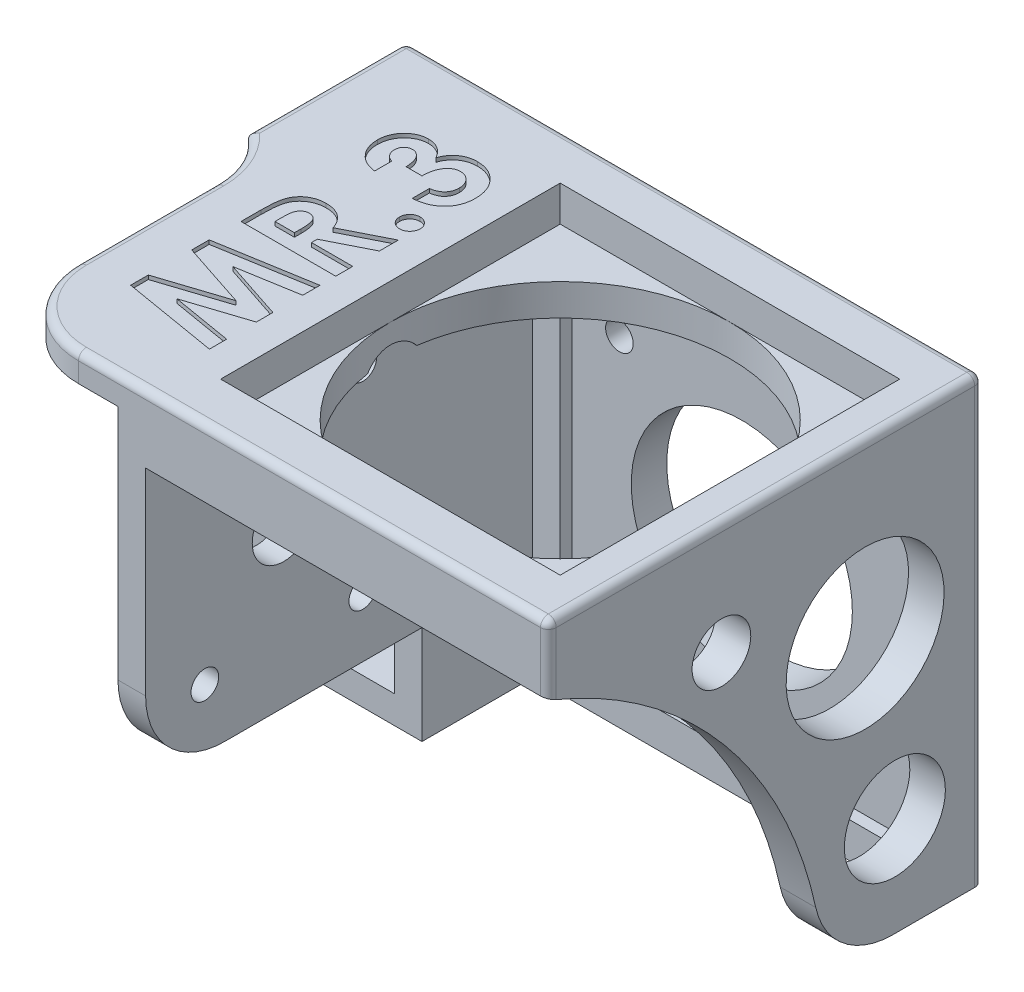
SolidWorks part; units mm, degrees
ref_plane "Front Plane" through (0, 0, 0) normal (0, 0, 1) x (1, 0, 0)
ref_plane "Top Plane" through (0, 0, 0) normal (0, 1, 0) x (1, 0, 0)
ref_plane "Right Plane" through (0, 0, 0) normal (1, 0, 0) x (0, 0, -1)
sketch "Sketch1" plane through (0, 0, 0) normal (0, 0, 1) x (1, 0, 0)
  line L0 (-36.7771, -12.6028) -> (36.2229, -12.6028)
  line L1 (-36.7771, 43.3972) -> (-14.7771, 43.3972)
  line L2 (-36.7771, 43.3972) -> (-36.7771, -12.6028)
  line L3 (36.2229, -12.6028) -> (36.2229, 43.3972)
  line L5 (-33.2771, 39.8972) -> (-18.2771, 39.8972)
  line L6 (-33.2771, 39.8972) -> (-33.2771, 24.8972)
  line L7 (-33.2771, 24.8972) -> (-18.2771, 24.8972)
  line L8 (-18.2771, 39.8972) -> (-18.2771, 24.8972)
  line L9 (-14.7771, 43.3972) -> (36.2229, 43.3972)
  dimension "D1" = 22
  dimension "D3" = 15
  dimension "D4" = 15
  dimension "D5" = 3.5
  dimension "D6" = 51
  dimension "D11" = 3.5
extrude "Boss-Extrude2" add sketch "Sketch1" along normal blind 20 contours L3 L9 L1 L2 L5 L8 L7 L6 region at (1.2081, 14.407, 0)
sketch "Sketch2" plane through (0, 0, 20) normal (0, 0, 1) x (1, 0, 0)
  line L0 (36.2229, -12.6028) -> (36.2229, 43.3972) construction
  line L1 (31.7229, -8.1028) -> (-11.2771, -8.1028)
  line L2 (31.7229, -8.1028) -> (31.7229, 34.8972)
  line L3 (31.7229, 34.8972) -> (-11.2771, 34.8972)
  line L4 (-11.2771, -8.1028) -> (-11.2771, 34.8972)
  line L5 (-36.7771, -12.6028) -> (36.2229, -12.6028) construction
  line L6 (-14.7771, 43.3972) -> (-14.7771, -12.6028) construction
  line L7 (-36.7771, 43.3972) -> (36.2229, 43.3972) construction
  line L8 (-18.2771, 39.8972) -> (-18.2771, 24.8972) construction
  line L9 (-33.2771, 24.8972) -> (-18.2771, 24.8972) construction
  line L10 (-33.2771, 14.8972) -> (-18.2771, 14.8972)
  line L11 (-33.2771, 14.8972) -> (-33.2771, -0.1028)
  line L12 (-33.2771, -0.1028) -> (-18.2771, -0.1028)
  line L13 (-18.2771, 14.8972) -> (-18.2771, -0.1028)
  line L14 (-36.7771, 43.3972) -> (-36.7771, -12.6028) construction
  dimension "D1" = 43
  dimension "D2" = 4.5
  dimension "D3" = 4.5
  dimension "D4" = 3.5
  dimension "D5" = 15
  dimension "D6" = 10
  dimension "D7" = 3.5
  dimension "D8" = 15
extrude "Cut-Extrude1" cut sketch "Sketch2" against normal offset from surface (15.5 mm away) 4.5 up to face at (-0.2771, 15.3972, 0)
sketch "Sketch3" plane through (0, 0, 4.5) normal (0, 0, 1) x (1, 0, 0)
  line L0 (-11.2771, -8.1028) -> (31.7229, 34.8972) construction
  line L1 (-11.2771, 34.8972) -> (31.7229, -8.1028) construction
  circle A0 centre (10.2229, 13.3972) radius 14
  circle A1 centre (25.7229, 28.8972) radius 1.75
  circle A2 centre (-5.2771, 28.8972) radius 1.75
  circle A3 centre (-5.2771, -2.1028) radius 1.75
  circle A4 centre (25.7229, -2.1028) radius 1.75
  dimension "D1" = 28
  dimension "D2" = 3.5
  dimension "D3" = 31
extrude "Cut-Extrude2" cut sketch "Sketch3" against normal blind 4.5
sketch "Sketch5" plane through (0, 0, 20) normal (0, 0, 1) x (1, 0, 0)
  line L0 (-33.2771, 39.8972) -> (-33.2771, 43.3972)
  line L1 (-33.2771, 43.3972) -> (-18.2771, 43.3972)
  line L2 (36.2229, -12.6028) -> (36.2229, 43.3972) construction
  line L3 (-33.2771, 39.8972) -> (-18.2771, 39.8972)
  line L4 (-14.7771, 43.3972) -> (36.2229, 43.3972)
  line L5 (-18.2771, 43.3972) -> (-14.7771, 43.3972)
  line L6 (-18.2771, 39.8972) -> (-18.2771, -0.1028)
  line L7 (-18.2771, -0.1028) -> (-14.7771, -0.1028)
  line L8 (-14.7771, 34.8972) -> (-14.7771, -0.1028)
  line L9 (31.7229, 34.8972) -> (-11.2771, 34.8972) construction
  line L10 (-14.7771, 34.8972) -> (36.2229, 34.8972)
  line L11 (36.2229, 43.3972) -> (36.2229, 34.8972)
  dimension "D1" = 3.5
extrude "Boss-Extrude3" add sketch "Sketch5" along normal blind 35
sketch "Sketch6" plane through (0, 43.3972, 0) normal (0, 1, 0) x (1, 0, 0)
  line L0 (36.2229, -55) -> (36.2229, 0) construction
  line L1 (31.7229, -6) -> (-11.2771, -6)
  line L2 (31.7229, -6) -> (31.7229, -49)
  line L3 (31.7229, -49) -> (-11.2771, -49)
  line L4 (-11.2771, -6) -> (-11.2771, -49)
  line L5 (-36.7771, 0) -> (36.2229, 0) construction
  dimension "D1" = 43
  dimension "D2" = 43
  dimension "D3" = 4.5
  dimension "D4" = 6
extrude "Cut-Extrude3" cut sketch "Sketch6" against normal offset from surface (4.5 mm away) 4 up to face at (9.9729, 34.8972, 25.125)
sketch "Sketch7" plane through (0, 38.8972, 0) normal (0, 1, 0) x (1, 0, 0)
  line L0 (-11.2771, -6) -> (31.7229, -49) construction
  line L1 (31.7229, -6) -> (-11.2771, -49) construction
  circle A0 centre (10.2229, -27.5) radius 21.5
extrude "Cut-Extrude4" cut sketch "Sketch7" against normal blind 4
sketch "Sketch8" plane through (-18.2771, 0, 0) normal (-1, 0, 0) x (0, 0, 1)
  line L0 (20, 24.8972) -> (55, 24.8972) construction
  line L1 (55, 39.8972) -> (55, -0.1028) construction
  line L2 (20, 14.8972) -> (55, 14.8972) construction
  line L3 (55, 32.3972) -> (20, 32.3972) construction
  line L4 (20, 43.3972) -> (20, -12.6028) construction
  line L5 (55, 7.3972) -> (23.2569, 7.3972) construction
  circle A0 centre (37.5, 19.8972) radius 4
  circle A1 centre (27.5, 32.3972) radius 1.75
  circle A2 centre (27.5, 7.3972) radius 1.75
  circle A3 centre (47.5, 7.3972) radius 1.75
  circle A4 centre (47.5, 32.3972) radius 1.75
  dimension "D2" = 8
  dimension "D7" = 17.5
  dimension "D8" = 3.5
  dimension "D1" = 5
  dimension "D3" = 20
  dimension "D4" = 20
  dimension "D5" = 7.5
  dimension "D6" = 7.5
  dimension "D9" = 7.5
  dimension "D10" = 7.5
extrude "Cut-Extrude5" cut sketch "Sketch8" against normal blind 4
sketch "Sketch9" plane through (0, 0, 20) normal (0, 0, 1) x (1, 0, 0)
  line L0 (-36.7771, -12.6028) -> (36.2229, -12.6028) construction
  line L1 (-11.2771, -8.1028) -> (31.7229, -8.1028)
  line L2 (-11.2771, -8.1028) -> (-11.2771, -12.6028)
  line L3 (-11.2771, -12.6028) -> (31.7229, -12.6028)
  line L4 (31.7229, -8.1028) -> (31.7229, -12.6028)
  line L5 (36.2229, -12.6028) -> (36.2229, 34.8972) construction
  dimension "D1" = 4.5
extrude "Cut-Extrude6" cut sketch "Sketch9" against normal offset from surface (14 mm away) 6 up to face at (27.4729, -2.1028, 0)
fillet "Fillet2" radius 10 1 edges at (-16.5271, -0.1028, 55)
sketch "Sketch10" plane through (-14.7771, 0, 0) normal (1, 0, 0) x (0, 0, -1)
  circle A0 centre (-27.5, 32.3972) radius 4
  circle A1 centre (-47.5, 32.3972) radius 4
  dimension "D1" = 8
  dimension "D2" = 8
extrude "Cut-Extrude7" cut sketch "Sketch10" along normal blind 9
sketch "Sketch11" plane through (36.2229, 0, 0) normal (1, 0, 0) x (0, 0, -1)
  line L1 (-20, -12.6028) -> (-20, 34.8972)
  line L2 (-20, 34.8972) -> (-55, 34.8972)
  arc A0 (-55, 34.8972) -> (-20, -12.6028) centre (-75.0615, -16.5297) cw
extrude "Boss-Extrude4" add sketch "Sketch11" against normal up to surface (4.5 mm away) up to face at (31.7229, 0.7722, 8.875)
fillet "Fillet3" radius 10 2 edges at (-33.2771, 41.6472, 55)
sketch "Sketch12" plane through (0, 0, 20) normal (0, 0, 1) x (1, 0, 0)
  line L1 (-14.7771, 34.8972) -> (-11.2771, 34.8972)
  line L2 (-14.7771, 34.8972) -> (-14.7771, -12.6028)
  line L3 (-14.7771, -12.6028) -> (-11.2771, -12.6028)
  line L4 (-11.2771, 34.8972) -> (-11.2771, -12.6028)
extrude "Cut-Extrude8" cut sketch "Sketch12" against normal offset from surface (14 mm away) 6 up to face at (27.4729, -2.1028, 0)
sketch "Sketch13" plane through (0, 43.3972, 0) normal (0, 1, 0) x (1, 0, 0)
  line L0 (-15.2771, 0) -> (-15.2771, -55) construction
  line L1 (-36.7771, 0) -> (36.2229, 0) construction
  line L2 (36.2229, -55) -> (-23.2771, -55) construction
  line L3 (-11.2771, -6) -> (-11.2771, -49) construction
  text T0 "MR.3" font "Century Gothic" height 12
  dimension "D1" = 4
extrude "Cut-Extrude9" cut sketch "Sketch13" against normal blind 0.5
sketch "Sketch15" plane through (36.2229, 0, 0) normal (1, 0, 0) x (0, 0, -1)
  line L0 (0, 43.3972) -> (-30.6213, 16.2157) construction
  line L1 (0, 34.8972) -> (-55, 34.8972) construction
  line L5 (0, 34.8972) -> (-27.1159, 10.8273) construction
  arc A0 (-20, -12.6028) -> (-55, 34.8972) centre (-75.0615, -16.5297) ccw construction
  circle A1 centre (-14.8861, 21.6832) radius 10
  circle A2 centre (-33.0796, 29.1831) radius 3.7169
  circle A4 centre (-11.1177, 0) radius 6.397
extrude "Cut-Extrude10" cut sketch "Sketch15" against normal blind 4.5
fillet "Fillet4" radius 10 1 edges at (33.9729, -12.6028, 20)
sketch "Sketch17" plane through (0, 0, 20) normal (0, 0, 1) x (1, 0, 0)
  line L1 (-33.2771, -3.6028) -> (-18.2771, -3.6028)
  line L2 (-33.2771, -3.6028) -> (-33.2771, -9.1028)
  line L3 (-33.2771, -9.1028) -> (-18.2771, -9.1028)
  line L4 (-18.2771, -3.6028) -> (-18.2771, -9.1028)
  line L10 (-36.7771, 39.8972) -> (-36.7771, -12.6028) construction
  line L11 (-33.2771, -0.1028) -> (-18.2771, -0.1028) construction
  line L12 (-36.7771, -12.6028) -> (-14.7771, -12.6028) construction
  line L13 (-14.7771, -0.1028) -> (-14.7771, -12.6028) construction
  dimension "D5" = 3.5
  dimension "D6" = 3.5
  dimension "D7" = 3.5
  dimension "D8" = 3.5
extrude "Cut-Extrude12" cut sketch "Sketch17" against normal offset from surface (15.5 mm away) 4.5 up to face at (27.4729, -2.1028, 0)
fillet "Fillet5" radius 1 8 edges at (-34.1942, 43.3972, 23.416) (-30.3482, 43.3972, 52.0711) (-36.7771, 43.3972, 10) (6.4729, 43.3972, 55) (36.2229, 15.3972, 0) (-0.2771, 43.3972, 0) (36.2229, 43.3972, 27.5)
fillet "Fillet6" radius 1 4 edges at (35.93, 43.1043, 54.7071) (36.2229, 38.6472, 55) (-36.4842, 43.1043, 0.2929) (-36.7771, 14.8972, 0)
